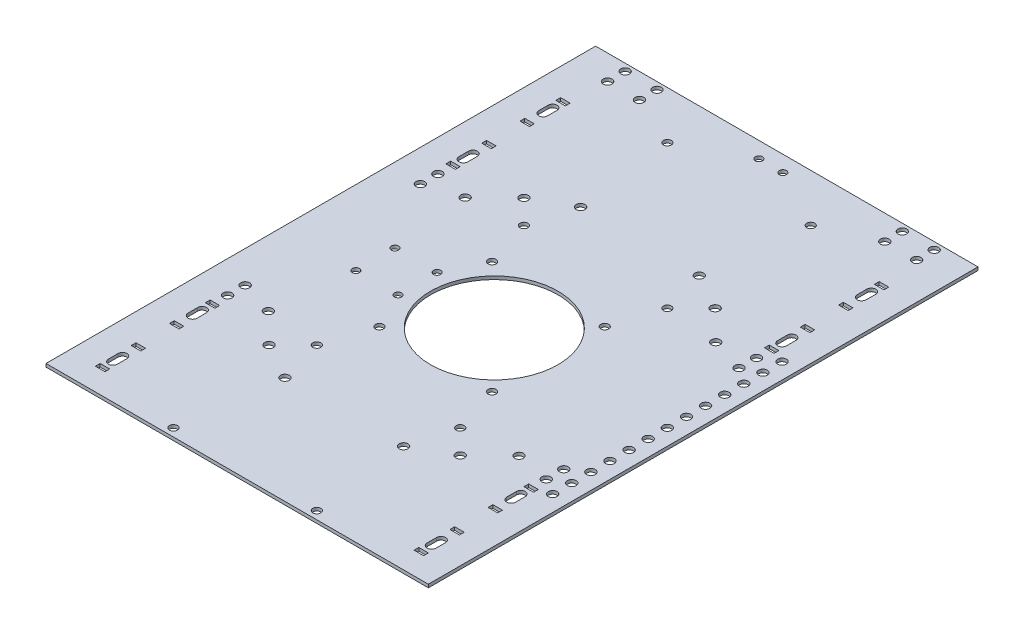
SolidWorks part; units mm, degrees
ref_plane "前视基准面" through (0, 0, 0) normal (0, 0, 1) x (1, 0, 0)
ref_plane "上视基准面" through (0, 0, 0) normal (0, 1, 0) x (1, 0, 0)
ref_plane "右视基准面" through (0, 0, 0) normal (1, 0, 0) x (0, 0, -1)
sketch "草图1" plane through (0, 0, 0) normal (0, 1, 0) x (1, 0, 0)
  line L2 (-120, 140) -> (-120, -140)
  line L3 (-120, -140) -> (120, -140)
  line L4 (120, 140) -> (120, -140)
  line L5 (-120, 140) -> (120, -140) construction
  line L6 (-120, -140) -> (120, 140) construction
  line L7 (-120, 185) -> (120, 185)
  line L8 (-120, 185) -> (-120, 140)
  line L10 (120, 185) -> (120, 140)
  line L11 (-120, 185) -> (120, 140) construction
  line L12 (-120, 140) -> (120, 185) construction
  point P0 (0, 0)
  point P6 (0, 162.5)
  dimension "D1" = 240
  dimension "D2" = 280
  dimension "D3" = 45
base flange "基体-法兰1" sketch "草图1" thickness 2 reverse thickness direction no parameters "D1"=2.7366
sketch "草图6" plane through (0, 0, 0) normal (0, 1, 0) x (1, 0, 0)
  line L0 (0, 0) -> (170.3975, 0) construction
  line L1 (0, 0) -> (0, -100) construction
  circle A0 centre (0, 0) radius 100 construction
  circle A1 centre (-60, -80) radius 2.75
  circle A2 centre (-78.6611, -61.7449) radius 2.75
  circle A3 centre (-37.25, -92.8032) radius 2.75
  circle A4 centre (37.25, -92.8032) radius 2.75
  circle A5 centre (78.6611, -61.7449) radius 2.75
  circle A6 centre (60, -80) radius 2.75
  circle A7 centre (78.6611, 61.7449) radius 2.75
  circle A8 centre (37.25, 92.8032) radius 2.75
  circle A9 centre (-60, 80) radius 2.75
  circle A10 centre (60, 80) radius 2.75
  circle A11 centre (-78.6611, 61.7449) radius 2.75
  circle A12 centre (-37.25, 92.8032) radius 2.75
  point P10 (0, 0)
  point P12 (0, 0)
  point P13 (0, 0)
  point P15 (0, 0)
  dimension "D1" = 200
  dimension "D2" = 5.5
  dimension "D3" = 80
  dimension "D4" = 2
  dimension "D5" = 2
extrude "切除-拉伸1" cut sketch "草图6" against normal blind 10 normal cut yes
sketch "草图7" plane through (0, 0, 0) normal (0, 1, 0) x (1, 0, 0)
  circle A0 centre (0, 0) radius 50 construction
  circle A1 centre (-35.3553, 35.3553) radius 2.5
  circle A2 centre (35.3553, 35.3553) radius 2.5
  circle A3 centre (35.3553, -35.3553) radius 2.5
  circle A4 centre (-35.3553, -35.3553) radius 2.5
  circle A5 centre (1.3845, 0) radius 40
  dimension "D2" = 100
  dimension "D3" = 5
  dimension "D1" = 80
  dimension "D4" = 4
extrude "切除-拉伸2" cut sketch "草图7" against normal blind 10 normal cut yes
sketch "草图9" plane through (0, 0, 0) normal (0, 1, 0) x (1, 0, 0)
  line L0 (120, -140) -> (120, 185) construction
  line L1 (-120, -140) -> (120, -140)
  line L2 (-120, -140) -> (-120, -160)
  line L3 (-120, -160) -> (120, -160)
  line L4 (120, -140) -> (120, -160)
  dimension "D1" = 20
extrude "凸台-拉伸1" add sketch "草图9" against normal blind 2
extrude "切除-拉伸3" cut sketch "草图8" against normal blind 10 normal cut yes
sketch "草图8" plane through (0, 0, 0) normal (0, 1, 0) x (1, 0, 0)
  line L0 (120, -160) -> (120, 185) construction
  line L1 (100, -110) -> (120, -110) construction
  line L2 (0, 0) -> (0, -160) construction
  line L3 (0, 0) -> (-120, 0) construction
  line L4 (-120, 185) -> (-120, -160) construction
  line L5 (100, -132) -> (100, -138) construction
  line L6 (110, -120) -> (90, -120) construction
  line L7 (110, -120) -> (110, -100) construction
  line L8 (110, -100) -> (90, -100) construction
  line L9 (90, -120) -> (90, -100) construction
  line L10 (110, -120) -> (90, -100) construction
  line L11 (110, -100) -> (90, -120) construction
  line L12 (102.8, -132) -> (102.8, -138)
  line L13 (97.2, -132) -> (97.2, -138)
  line L14 (-120, -160) -> (120, -160) construction
  line L15 (103, -146) -> (97, -146)
  line L16 (103, -146) -> (103, -143)
  line L17 (103, -143) -> (97, -143)
  line L18 (97, -146) -> (97, -143)
  line L19 (103, -146) -> (97, -143) construction
  line L20 (103, -143) -> (97, -146) construction
  line L21 (103, -123.5) -> (97, -123.5)
  line L22 (103, -123.5) -> (103, -120.5)
  line L23 (103, -120.5) -> (97, -120.5)
  line L24 (97, -123.5) -> (97, -120.5)
  line L25 (103, -123.5) -> (97, -120.5) construction
  line L26 (103, -120.5) -> (97, -123.5) construction
  line L27 (120, -160) -> (120, 185) construction
  line L28 (103, -99.5) -> (97, -96.5) construction
  line L29 (103, -96.5) -> (97, -99.5) construction
  line L30 (103, -77) -> (97, -74) construction
  line L31 (103, -74) -> (97, -77) construction
  line L32 (97, -96.5) -> (97, -99.5)
  line L33 (103, -99.5) -> (97, -99.5)
  line L34 (103, -96.5) -> (103, -99.5)
  line L35 (103, -96.5) -> (97, -96.5)
  line L36 (97, -74) -> (97, -77)
  line L37 (103, -77) -> (97, -77)
  line L38 (103, -74) -> (103, -77)
  line L39 (103, -74) -> (97, -74)
  line L40 (100, -88) -> (100, -82) construction
  line L41 (102.8, -88) -> (102.8, -82)
  line L42 (97.2, -88) -> (97.2, -82)
  arc A0 (102.8, -88) -> (97.2, -88) centre (100, -88) cw
  arc A1 (97.2, -82) -> (102.8, -82) centre (100, -82) cw
  arc A2 (102.8, -132) -> (97.2, -132) centre (100, -132) ccw
  arc A3 (97.2, -138) -> (102.8, -138) centre (100, -138) ccw
  circle A4 centre (100, -66) radius 2.75
  circle A5 centre (100, -55) radius 2.75
  point P11 (100, -110)
  point P21 (100, -135)
  point P26 (100, -144.5)
  point P31 (100, -122)
  point P44 (100, -98)
  point P45 (100, -75.5)
  point P48 (100, -85)
  dimension "D9" = 2.8
  dimension "D17" = 5.5
  dimension "D2" = 19
  dimension "D3" = 25
  dimension "D5" = 20
  dimension "D6" = 20
  dimension "D7" = 110
  dimension "D8" = 10
  dimension "D10" = 6
  dimension "D11" = 6
  dimension "D12" = 6.5
  dimension "D13" = 3
  dimension "D14" = 10
  dimension "D15" = 3
  dimension "D16" = 6
  dimension "D4" = 11
mirror "镜向1" about plane through (0, 0, 0) normal (0, 0, 1) of "切除-拉伸3"
mirror "镜向2" about plane through (0, 0, 0) normal (1, 0, 0) of "镜向1", "切除-拉伸3"
sketch "草图10" plane through (0, 0, 0) normal (0, 1, 0) x (1, 0, 0)
  line L0 (120, 185) -> (-120, 185) construction
  line L1 (-120, 185) -> (-120, -160) construction
  circle A0 centre (-97, 180.5) radius 2.75
  circle A1 centre (-77, 180.5) radius 2.75
  circle A2 centre (-97, 169.5) radius 2.75
  circle A3 centre (-77, 169.5) radius 2.75
  dimension "D3" = 5.5
  dimension "D4" = 20
  dimension "D1" = 4.5
  dimension "D2" = 23
  dimension "D5" = 2
extrude "切除-拉伸4" cut sketch "草图10" against normal blind 10 normal cut yes
mirror "镜向3" about plane through (0, 0, 0) normal (1, 0, 0) of "切除-拉伸4"
sketch "草图11" plane through (0, 0, 0) normal (0, 1, 0) x (1, 0, 0)
  line L0 (120, -160) -> (120, 185) construction
  circle A0 centre (110, 72) radius 2.75
  circle A1 centre (110, 60) radius 2.75
  circle A2 centre (110, 48) radius 2.75
  circle A3 centre (110, 36) radius 2.75
  circle A4 centre (110, 24) radius 2.75
  circle A5 centre (110, 12) radius 2.75
  circle A6 centre (110, 0) radius 2.75
  circle A7 centre (110, -12) radius 2.75
  circle A8 centre (110, -24) radius 2.75
  circle A9 centre (110, -36) radius 2.75
  circle A10 centre (110, -48) radius 2.75
  circle A11 centre (110, -60) radius 2.75
  circle A12 centre (110, -72) radius 2.75
  dimension "D2" = 5.5
  dimension "D1" = 10
  dimension "D4" = 72
  dimension "D3" = 13
extrude "切除-拉伸5" cut sketch "草图11" against normal blind 10 normal cut yes
sketch "草图12" plane through (0, 0, 0) normal (0, 1, 0) x (1, 0, 0)
  line L0 (-46.75, 0) -> (-73.25, 0) construction
  line L1 (-120, 185) -> (-120, -160) construction
  line L2 (0, 185) -> (0, 140.1837) construction
  line L3 (120, 185) -> (-120, 185) construction
  circle A0 centre (-73.25, 12.25) radius 2.25
  circle A1 centre (-73.25, -12.25) radius 2.25
  circle A2 centre (-46.75, 12.25) radius 2.25
  circle A3 centre (-46.75, -12.25) radius 2.25
  circle A4 centre (7.5, 175) radius 2.25
  circle A5 centre (-7.5, 175) radius 2.25
  point P16 (-60, 0)
  dimension "D3" = 4.5
  dimension "D5" = 4.5
  dimension "D1" = 24.5
  dimension "D4" = 60
  dimension "D6" = 15
  dimension "D7" = 10
  dimension "D8" = 26.5
  dimension "D2" = 2
extrude "切除-拉伸6" cut sketch "草图12" against normal blind 10 normal cut yes
sketch "草图13" plane through (0, 0, 0) normal (0, 1, 0) x (1, 0, 0)
  line L0 (0, 185) -> (0, 0) construction
  line L1 (0, 0) -> (-120, 0) construction
  line L2 (-45, 110) -> (0, 110) construction
  line L3 (120, 185) -> (-120, 185) construction
  line L4 (-120, 185) -> (-120, -160) construction
  circle A0 centre (-45, 155) radius 2.5
  circle A1 centre (-45, 65) radius 2.5
  circle A2 centre (45, 65) radius 2.5
  circle A3 centre (45, 155) radius 2.5
  dimension "D3" = 5
  dimension "D1" = 90
  dimension "D2" = 90
  dimension "D4" = 110
extrude "切除-拉伸7" cut sketch "草图13" against normal blind 3 normal cut yes
mirror "镜向4" about plane through (0, 0, 0) normal (0, 0, 1) of "切除-拉伸7"
sketch "折弯-线1" plane through (0, 0, 0) normal (0, 1, 0) x (1, 0, 0)
sketch "边界框1" plane through (0, 0, 0) normal (0, 1, 0) x (1, 0, 0)
sheet metal parameters "钣金6" thickness 2 parameters "D1"=2.7366
flat pattern "平板型式6" [suppressed]
sketch "折弯-线2" plane through (0, 0, 0) normal (0, 1, 0) x (1, 0, 0)
sketch "边界框2" [suppressed] plane through (0, 0, 0) normal (0, 1, 0) x (1, 0, 0)
sheet metal parameters "钣金7" thickness 2 parameters "D1"=2.7366
flat pattern "平板型式6"
sketch "折弯-线2" plane through (0, 0, 0) normal (0, 1, 0) x (1, 0, 0)
sketch "边界框2" [suppressed] plane through (0, 0, 0) normal (0, 1, 0) x (1, 0, 0)
sheet metal parameters "钣金8" thickness 2 parameters "D1"=2.7366
flat pattern "平板型式6"
sketch "折弯-线2" plane through (0, 0, 0) normal (0, 1, 0) x (1, 0, 0)
sketch "边界框2" [suppressed] plane through (0, 0, 0) normal (0, 1, 0) x (1, 0, 0)
sheet metal parameters "钣金11" thickness 2 parameters "D1"=2.7366
flat pattern "平板型式6"
sketch "折弯-线2" plane through (0, 0, 0) normal (0, 1, 0) x (1, 0, 0)
sketch "边界框2" [suppressed] plane through (0, 0, 0) normal (0, 1, 0) x (1, 0, 0)
sheet metal parameters "钣金12" thickness 2 parameters "D1"=2.7366
flat pattern "平板型式6"
sketch "折弯-线2" plane through (0, 0, 0) normal (0, 1, 0) x (1, 0, 0)
sketch "边界框2" [suppressed] plane through (0, 0, 0) normal (0, 1, 0) x (1, 0, 0)
sheet metal parameters "钣金13" thickness 2 parameters "D1"=2.7366
flat pattern "平板型式6"
sketch "折弯-线2" plane through (0, 0, 0) normal (0, 1, 0) x (1, 0, 0)
sketch "边界框2" [suppressed] plane through (0, 0, 0) normal (0, 1, 0) x (1, 0, 0)
sheet metal parameters "钣金14" thickness 2 parameters "D1"=2.7366
flat pattern "平板型式6"
sketch "折弯-线2" plane through (0, 0, 0) normal (0, 1, 0) x (1, 0, 0)
sketch "边界框2" [suppressed] plane through (0, 0, 0) normal (0, 1, 0) x (1, 0, 0)
sheet metal parameters "钣金15" thickness 2 parameters "D1"=2.7366
flat pattern "平板型式6"
sketch "折弯-线2" plane through (0, 0, 0) normal (0, 1, 0) x (1, 0, 0)
sketch "边界框2" [suppressed] plane through (0, 0, 0) normal (0, 1, 0) x (1, 0, 0)
sheet metal parameters "钣金16" thickness 2 parameters "D1"=2.7366
flat pattern "平板型式6"
sketch "折弯-线2" plane through (0, 0, 0) normal (0, 1, 0) x (1, 0, 0)
sketch "边界框2" [suppressed] plane through (0, 0, 0) normal (0, 1, 0) x (1, 0, 0)
sheet metal parameters "钣金17" thickness 2 parameters "D1"=2.7366
flat pattern "平板型式6"
sketch "折弯-线2" plane through (0, 0, 0) normal (0, 1, 0) x (1, 0, 0)
sketch "边界框2" [suppressed] plane through (0, 0, 0) normal (0, 1, 0) x (1, 0, 0)
sheet metal parameters "钣金18" thickness 2 parameters "D1"=2.7366
flat pattern "平板型式6"
sketch "折弯-线2" plane through (0, 0, 0) normal (0, 1, 0) x (1, 0, 0)
sketch "边界框2" [suppressed] plane through (0, 0, 0) normal (0, 1, 0) x (1, 0, 0)
sheet metal parameters "钣金19" thickness 2 parameters "D1"=2.7366
flat pattern "平板型式6"
sketch "折弯-线2" plane through (0, 0, 0) normal (0, 1, 0) x (1, 0, 0)
sketch "边界框2" [suppressed] plane through (0, 0, 0) normal (0, 1, 0) x (1, 0, 0)
sheet metal parameters "钣金20" thickness 2 parameters "D1"=2.7366
flat pattern "平板型式6"
sketch "折弯-线2" plane through (0, 0, 0) normal (0, 1, 0) x (1, 0, 0)
sketch "边界框2" [suppressed] plane through (0, 0, 0) normal (0, 1, 0) x (1, 0, 0)
